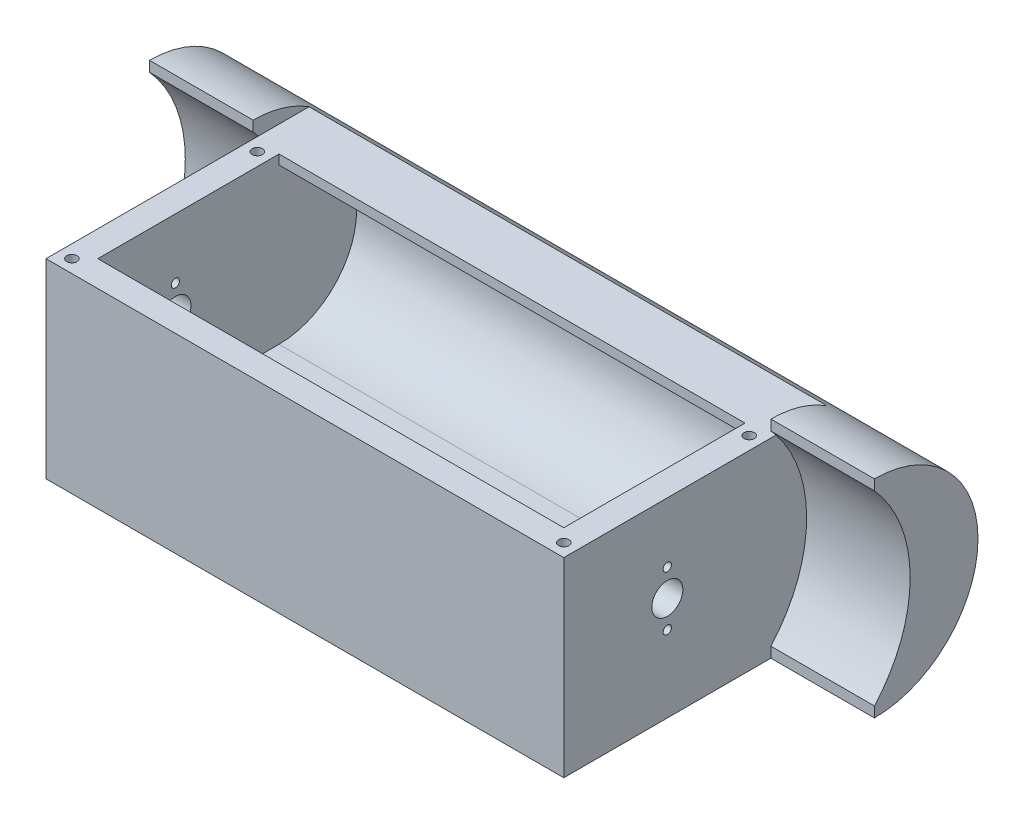
SolidWorks part; units mm, degrees
ref_plane "Front Plane" through (0, 0, 0) normal (0, 0, 1) x (1, 0, 0)
ref_plane "Top Plane" through (0, 0, 0) normal (0, 1, 0) x (1, 0, 0)
ref_plane "Right Plane" through (0, 0, 0) normal (1, 0, 0) x (0, 0, -1)
sketch "Sketch1" plane through (0, 0, 0) normal (1, 0, 0) x (0, 0, -1)
  line L1 (-20, 20) -> (20, 20)
  line L2 (-20, 20) -> (-20, -20)
  line L3 (-20, -20) -> (20, -20)
  arc A0 (20, 20) -> (20, -20) centre (20, 0) cw
  dimension "D1" = 40
  dimension "D2" = 40
  dimension "D3" = 20
  dimension "D4" = 20
extrude "Boss-Extrude1" add sketch "Sketch1" along normal blind 100
shell "Shell3" thickness 5 removed face at (50, 20, 0)
sketch "Sketch9" plane through (100, 0, 0) normal (1, 0, 0) x (0, 0, -1)
  line L0 (20, 20) -> (20, -20)
  arc A0 (20, 20) -> (20, -20) centre (20, 0) cw
  arc A1 (20, -20) -> (20, 20) centre (20, 0) ccw construction
extrude "Boss-Extrude2" add sketch "Sketch9" along normal blind 20
ref_plane "Plane1" through (50, 0, 0) normal (1, 0, 0) x (0, 0, -1)
mirror "Mirror1" about plane through (50, 0, 0) normal (1, 0, 0) of "Boss-Extrude2"
sketch "Sketch7" plane through (0, 20, 0) normal (0, 1, 0) x (1, 0, 0)
  line L0 (0, 20) -> (0, 0) construction
  line L1 (0, 30.81) -> (100, 30.81)
  line L2 (0, 30.81) -> (0, -20)
  line L3 (0, -20) -> (100, -20)
  line L4 (100, 30.81) -> (100, -20)
  dimension "D1" = 50.81
extrude "Cut-Extrude6" cut sketch "Sketch7" against normal blind 3.175
sketch "Sketch2" plane through (100, 0, 0) normal (1, 0, 0) x (0, 0, -1)
  line L0 (0, 16.825) -> (0, -20) construction
  line L2 (-20, -20) -> (20, -20) construction
  line L3 (-20, 0) -> (40, 0) construction
  line L4 (-20, 16.825) -> (-20, -20) construction
  line L5 (-20, 16.825) -> (20, 16.825) construction
  circle A0 centre (0, -5.25) radius 0.8
  circle A1 centre (0, 0) radius 3
  circle A2 centre (0, 5.25) radius 0.8
  arc A4 (20, -20) -> (30.8129, 16.825) centre (20, 0) ccw construction
  dimension "D1" = 6
  dimension "D2" = 1.6
  dimension "D3" = 5.25
extrude "Cut-Extrude1" cut sketch "Sketch2" against normal up to surface (100 mm away) up to face at (0, -1.5875, 0)
sketch "Sketch8" plane through (0, 16.825, 0) normal (0, 1, 0) x (1, 0, 0)
  line L0 (0, -20) -> (100, -20) construction
  line L1 (100, -20) -> (100, 20) construction
  line L2 (50, -20) -> (50, 40) construction
  line L3 (120, 40) -> (-20, 40) construction
  circle A0 centre (97.5, -17.5) radius 1
  circle A1 centre (97.5, 18.31) radius 1
  circle A2 centre (2.5, -17.5) radius 1
  circle A3 centre (2.5, 18.31) radius 1
  dimension "D1" = 2
  dimension "D2" = 2.5
  dimension "D3" = 2.5
  dimension "D4" = 35.81
  dimension "D5" = 2.5
extrude "Cut-Extrude7" cut sketch "Sketch8" against normal blind 3
sketch "Sketch10" plane through (120, 0, 0) normal (1, 0, 0) x (0, 0, -1)
  line L0 (20, 17.9892) -> (20, -17.9892)
  line L1 (20, 20) -> (20, -20) construction
  arc A0 (20, -17.9892) -> (20, 17.9892) centre (0, 0) ccw
  dimension "D1" = 53.8
extrude "Cut-Extrude8" cut sketch "Sketch10" against normal up to surface (20 mm away) up to face at (100, -5.25, 0.8)
sketch "Sketch11" plane through (-20, 0, 0) normal (-1, 0, 0) x (0, 0, 1)
  line L0 (-20, 17.9892) -> (-20, -17.9892)
  line L1 (-20, 20) -> (-20, -20) construction
  line L2 (-20, 16.825) -> (-20, -20) construction
  arc A0 (-20, 17.9892) -> (-20, -17.9892) centre (0, 0) ccw
  dimension "D1" = 53.8
extrude "Cut-Extrude9" cut sketch "Sketch11" against normal up to surface (20 mm away) up to face at (0, -5.25, 0.8)
